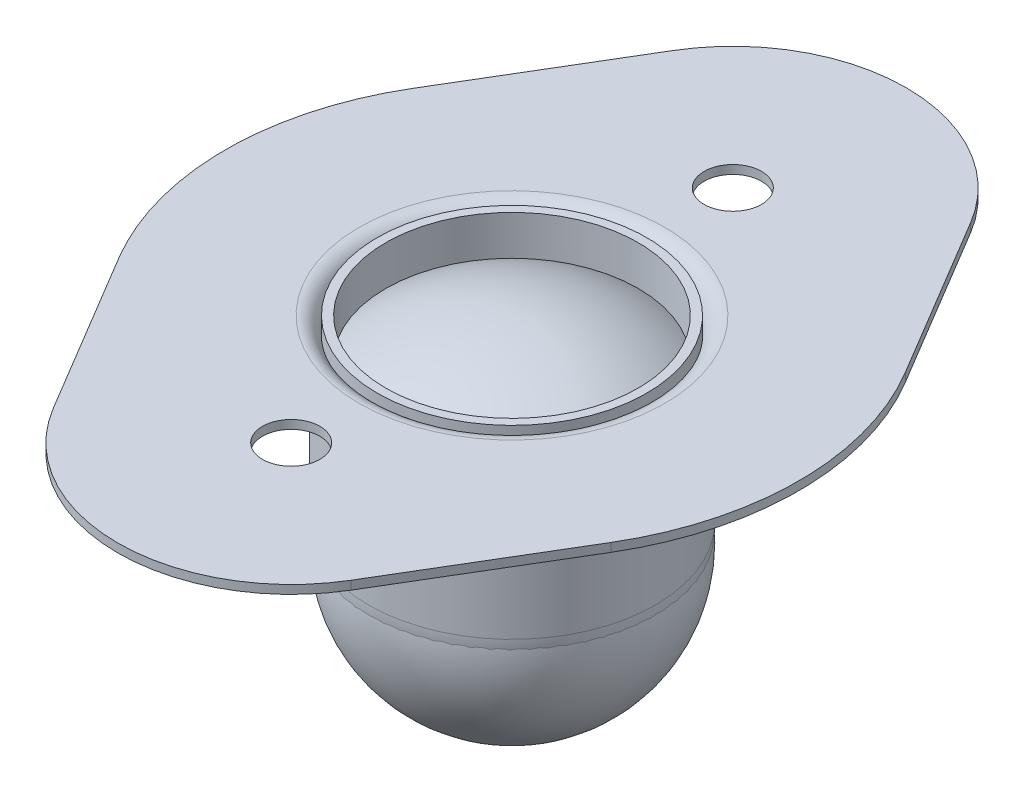
SolidWorks part; units mm, degrees
ref_plane "Front" through (0, 0, 0) normal (0, 0, 1) x (1, 0, 0)
ref_plane "Top" through (0, 0, 0) normal (0, 1, 0) x (1, 0, 0)
ref_plane "Right" through (0, 0, 0) normal (1, 0, 0) x (0, 0, -1)
sketch "Sketch1" plane through (0, 0, 0) normal (0, 1, 0) x (1, 0, 0)
  line L0 (0, -19.558) -> (0, 19.558) construction
  line L1 (21.8033, -13.0299) -> (13.191, -27.4411)
  line L2 (-13.191, -27.4411) -> (-21.8033, -13.0299)
  line L3 (-13.191, 27.4411) -> (-21.8033, 13.0299)
  line L4 (21.8033, 13.0299) -> (13.191, 27.4411)
  circle A0 centre (0, 0) radius 12.7 construction
  arc A1 (21.8033, -13.0299) -> (21.8033, 13.0299) centre (0, 0) ccw
  arc A2 (13.191, 27.4411) -> (-13.191, 27.4411) centre (0, 19.558) ccw
  arc A3 (-13.191, -27.4411) -> (13.191, -27.4411) centre (0, -19.558) ccw
  arc A4 (-21.8033, 13.0299) -> (-21.8033, -13.0299) centre (0, 0) ccw
  circle A5 centre (0, 19.558) radius 2.54
  circle A6 centre (0, -19.558) radius 2.54
  point P5 (0, 0)
  dimension "D1" = 25.4
  dimension "D3" = 50.8
  dimension "D4" = 69.85
  dimension "D5" = 5.08
  dimension "D2" = 39.116
extrude "Boss-Extrude1" add sketch "Sketch1" along normal blind 0.762
ref_axis "Axis1" through (0, -30.9086, 0) along (0, 1, 0)
sketch "Sketch2" plane through (0, 0, 0) normal (0, -1, 0) x (1, 0, 0)
  circle A0 centre (0, 0) radius 12.7 construction
  circle A1 centre (0, 0) radius 12.7
extrude "Boss-Extrude2" add sketch "Sketch2" along normal offset from surface (23.8442 mm away) 24.6062 up to face at (0, 0.762, -17.018)
fillet "Fillet1" radius 8.7312 1 edges at (0, -23.8442, 12.7)
shell "Shell1" thickness 0.762 removed face at (0, 0.762, -17.018)
fillet "Fillet2" radius 1.5875 2 edges at (0, 0, 12.7) (0, 0.762, 11.938)
sketch "Sketch6" plane through (0, -23.8443, 0) normal (0, -1, 0) x (1, 0, 0)
  circle A1 centre (0, 0) radius 3.9688
  circle A2 centre (0, 0) radius 3.9688
  dimension "D1" = 0
extrude "Cut-Extrude3" cut sketch "Sketch6" against normal up to surface (0.762 mm away) up to face at (0, -23.0822, 3.9688)
sketch "Sketch7" plane through (0, 0.762, 0) normal (0, 1, 0) x (1, 0, 0)
  circle A0 centre (0, 0) radius 11.938 construction
  circle A1 centre (0, 0) radius 11.938
extrude "Boss-Extrude3" add sketch "Sketch7" against normal blind 12.7 separate body
sketch "Sketch8" plane through (0, 0, 0) normal (1, 0, 0) x (0, 0, -1)
  line L0 (-11.938, -11.938) -> (11.938, -11.938) construction
  line L1 (0, 0) -> (0, -11.938)
  line L2 (0, -11.938) -> (-17.4625, -11.938)
  arc A0 (-17.4625, -11.938) -> (0, 0) centre (0, -18.7408) cw
  arc A1 (0, 0) -> (17.4625, -11.938) centre (0, -18.7408) cw construction
  dimension "D1" = 34.925
revolve "Cut-Revolve1" cut sketch "Sketch8" angle 360 about axis through (0, -30.9086, 0) along (0, 1, 0)
fillet "Fillet3" [suppressed] radius 1.1906
shell "Shell2" thickness 0.762 removed face at (0, 0.762, 11.938)
sketch "Sketch3" plane through (0, 0, 0) normal (1, 0, 0) x (0, 0, -1)
  line L0 (13.0299, 0.762) -> (-13.0299, 0.762) construction
  line L1 (0, -29.4005) -> (0, -4.0005)
  arc A0 (0, -4.0005) -> (0, -29.4005) centre (0, -16.7005) ccw
  point P8 (0, -16.7005)
  dimension "D1" = 25.4
  dimension "D2" = 30.1625
revolve "Revolve1" add sketch "Sketch3" angle 360 about axis through (0, -84.3715, 0) along (0, 1, 0)
